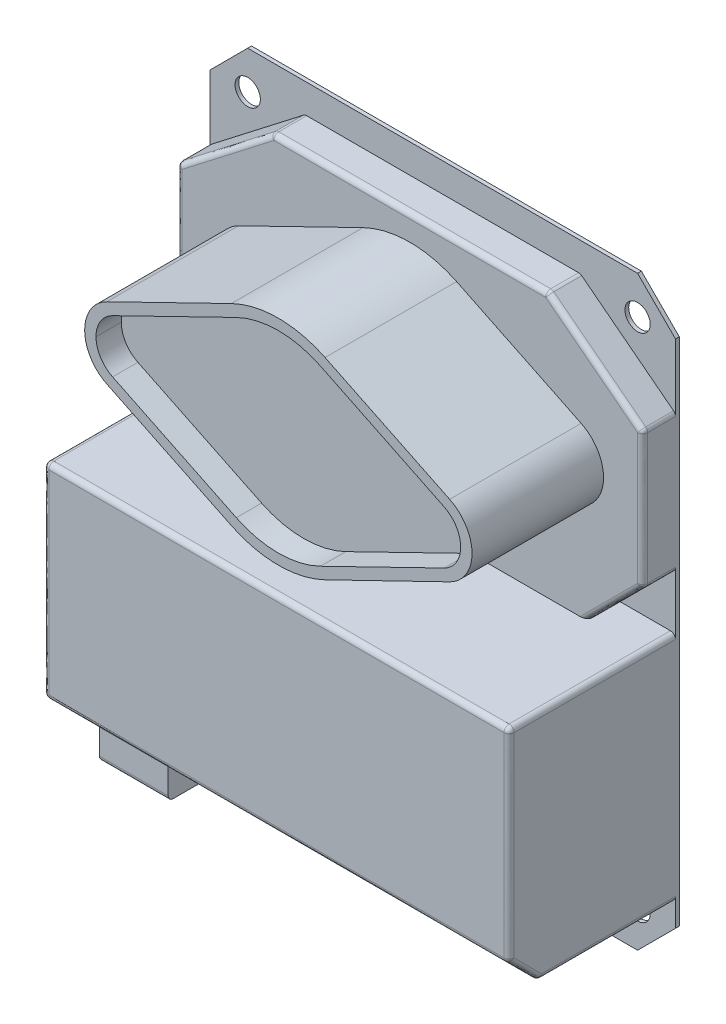
SolidWorks part; units mm, degrees
ref_plane "Front Plane" through (0, 0, 0) normal (0, 0, 1) x (1, 0, 0)
ref_plane "Top Plane" through (0, 0, 0) normal (0, 1, 0) x (1, 0, 0)
ref_plane "Right Plane" through (0, 0, 0) normal (1, 0, 0) x (0, 0, -1)
sketch "Sketch1" plane through (0, 0, 0) normal (0, 0, 1) x (1, 0, 0)
  line L0 (92.075, 231.8) -> (92.075, 0) construction
  line L1 (15, 0) -> (169.15, 0)
  line L2 (0, 15) -> (0, 216.8)
  line L3 (15, 231.8) -> (169.15, 231.8)
  line L4 (184.15, 15) -> (184.15, 216.8)
  line L5 (15, 231.8) -> (0, 216.8)
  line L6 (0, 115.9) -> (184.15, 115.9) construction
  line L7 (15, 0) -> (0, 15)
  line L8 (169.15, 0) -> (184.15, 15)
  line L9 (169.15, 231.8) -> (184.15, 216.8)
  circle A0 centre (15, 216.8) radius 5
  circle A1 centre (169.15, 216.8) radius 5
  circle A2 centre (169.15, 15) radius 5
  circle A3 centre (15, 15) radius 5
extrude "Boss-Extrude2" add sketch "Sketch1" along normal blind 1.5
sketch "Sketch2" plane through (184.15, 0, 0) normal (1, 0, 0) x (0, 0, -1)
  line L0 (-67.3002, 35.9457) -> (-55.267, 23.9125)
  line L2 (-1.5, 115.9) -> (-1.5, 23.9125)
  line L3 (-1.5, 15) -> (-1.5, 216.8) construction
  line L4 (-1.5, 115.9) -> (-67.3002, 115.9)
  line L5 (-67.3002, 115.9) -> (-67.3002, 35.9457)
  line L6 (-1.5, 23.9125) -> (-55.267, 23.9125)
extrude "Boss-Extrude4" add sketch "Sketch2" against normal blind 184
sketch "Sketch6" plane through (0, 23.9125, 0) normal (0, -1, 0) x (1, 0, 0)
  line L0 (22.1838, 55.267) -> (22.1838, 67.3002)
  line L1 (0.15, 55.267) -> (184.15, 55.267) construction
  line L2 (22.1838, 67.3002) -> (49.3485, 67.3002)
  line L3 (49.3485, 67.3002) -> (49.3485, 55.267)
  line L4 (22.1838, 55.267) -> (49.3485, 55.267)
extrude "Boss-Extrude5" add sketch "Sketch6" against normal blind 12
fillet "Fillet5" radius 2 13 edges at (35.7661, 23.9125, 67.3002) (0.15, 115.9, 34.4001) (184.15, 115.9, 34.4001) (184.15, 23.9125, 28.3835) (0.15, 23.9125, 28.3835) (184.15, 29.9291, 61.2836) (0.15, 29.9291, 61.2836) (11.1669, 23.9125, 55.267) (116.7492, 23.9125, 55.267) (92.15, 35.9457, 67.3002) (184.15, 75.9229, 67.3002) (92.15, 115.9, 67.3002) (0.15, 75.9229, 67.3002) first distance on face at (35.7661, 29.9125, 67.3002) first distance on face at (0.15, 63.1141, 38.5735) first distance on face at (184.15, 86.5745, 21.763) first distance on face at (63.9581, 29.9208, 61.2753) first distance on face at (92.15, 115.9, 34.4001)
sketch "Sketch7" plane through (0, 0, 1.5) normal (0, 0, 1) x (1, 0, 0)
  line L0 (92.075, 231.8) -> (92.075, 0) construction
  line L1 (169.15, 231.8) -> (15, 231.8) construction
  line L2 (15, 0) -> (169.15, 0) construction
  line L3 (184.15, 165.35) -> (0, 165.35) construction
  line L4 (184.15, 113.9) -> (184.15, 216.8) construction
  line L5 (0, 216.8) -> (0, 15) construction
  line L6 (37.6372, 220.3443) -> (146.5128, 220.3443)
  line L7 (146.5128, 220.3443) -> (184.15, 191.2343)
  line L8 (184.15, 191.2343) -> (184.15, 137.8125)
  line L9 (184.15, 137.8125) -> (162.2375, 115.9)
  line L10 (182.15, 115.9) -> (2.15, 115.9) construction
  line L11 (162.2375, 115.9) -> (21.9125, 115.9)
  line L12 (37.6372, 220.3443) -> (0, 191.2343)
  line L13 (0, 191.2343) -> (0, 137.8125)
  line L14 (0, 137.8125) -> (21.9125, 115.9)
  point P13 (92.075, 220.3443)
  point P24 (92.075, 115.9)
extrude "Boss-Extrude6" add sketch "Sketch7" along normal blind 13
sketch "Sketch9" plane through (0, 0, 14.5) normal (0, 0, 1) x (1, 0, 0)
  line L0 (92.075, 220.3443) -> (92.15, 115.9) construction
  line L1 (146.5128, 220.3443) -> (37.6372, 220.3443) construction
  line L2 (182.15, 115.9) -> (2.15, 115.9) construction
  line L3 (110.5933, 206.1777) -> (159.8433, 182.2605)
  line L4 (110.5933, 130.0667) -> (159.8433, 153.9839)
  line L5 (73.6864, 130.0402) -> (24.4021, 153.8866)
  line L6 (73.5771, 206.1511) -> (24.3614, 182.1632)
  line L9 (184.15, 137.8125) -> (184.15, 191.2343) construction
  line L10 (184.15, 168.1222) -> (0, 168.1222) construction
  line L11 (0, 191.2343) -> (0, 137.8125) construction
  arc A0 (73.6864, 130.0402) -> (110.5933, 130.0667) centre (92.1125, 168.1222) ccw
  arc A1 (159.8433, 182.2605) -> (159.8433, 153.9839) centre (152.9774, 168.1222) cw
  arc A2 (24.3614, 182.1632) -> (24.4021, 153.8866) centre (31.2477, 168.0348) ccw
  arc A3 (110.5933, 206.1777) -> (73.5771, 206.1511) centre (92.1125, 168.1222) ccw
extrude "Boss-Extrude7" add sketch "Sketch9" along normal blind 52
fillet "Fillet6" radius 2 13 edges at (10.9563, 126.8563, 14.5) (0, 164.5234, 14.5) (173.1937, 126.8563, 14.5) (184.15, 164.5234, 14.5) (165.3314, 205.7893, 14.5) (18.8186, 205.7893, 14.5) (92.075, 220.3443, 14.5) (184.15, 137.8125, 8) (184.15, 191.2343, 8) (0, 137.8125, 8) (0, 191.2343, 8) (146.5128, 220.3443, 8) (37.6372, 220.3443, 8) first distance on face at (92.075, 166.3228, 14.5) first distance on face at (173.1937, 126.8563, 8) first distance on face at (184.15, 114.0067, 17.1568) first distance on face at (165.3314, 205.7893, 8) first distance on face at (92.075, 220.3443, 8) first distance on face at (10.9563, 126.8563, 8) first distance on face at (0, 140.2117, 4.375)
sketch "Sketch12" plane through (0, 0, 66.5) normal (0, 0, 1) x (1, 0, 0)
  line L0 (92.0821, 210.4277) -> (92.1429, 125.8166) construction
  line L1 (168.6947, 168.1222) -> (15.5304, 168.0122) construction
  line L2 (108.7834, 133.8088) -> (157.6609, 157.6319)
  line L3 (108.7342, 202.3494) -> (157.6459, 178.5966)
  line L4 (75.4909, 133.7849) -> (26.5792, 157.5378)
  line L5 (75.4417, 202.3255) -> (26.5642, 178.5024)
  arc A0 (110.5933, 206.1777) -> (73.5771, 206.1511) centre (92.1125, 168.1222) ccw construction
  arc A1 (73.6864, 130.0402) -> (110.5933, 130.0667) centre (92.1125, 168.1222) ccw construction
  arc A2 (159.8433, 153.9839) -> (159.8433, 182.2605) centre (152.9774, 168.1222) ccw construction
  arc A3 (24.3614, 182.1632) -> (24.4021, 153.8866) centre (31.2477, 168.0348) ccw construction
  arc A4 (108.7342, 202.3494) -> (75.4417, 202.3255) centre (92.1125, 168.1222) ccw
  arc A5 (157.6459, 178.5966) -> (164.2054, 168.1189) centre (152.5576, 168.1189) cw
  arc A6 (157.6609, 157.6319) -> (164.2054, 168.1189) centre (152.5576, 168.1022) ccw
  arc A7 (26.5792, 157.5378) -> (20.0197, 168.0154) centre (31.6674, 168.0154) cw
  arc A8 (26.5642, 178.5024) -> (20.0197, 168.0154) centre (31.6674, 168.0321) ccw
  arc A9 (108.7834, 133.8088) -> (75.4909, 133.7849) centre (92.1126, 168.0122) cw
extrude "Cut-Extrude1" cut sketch "Sketch12" against normal blind 10
